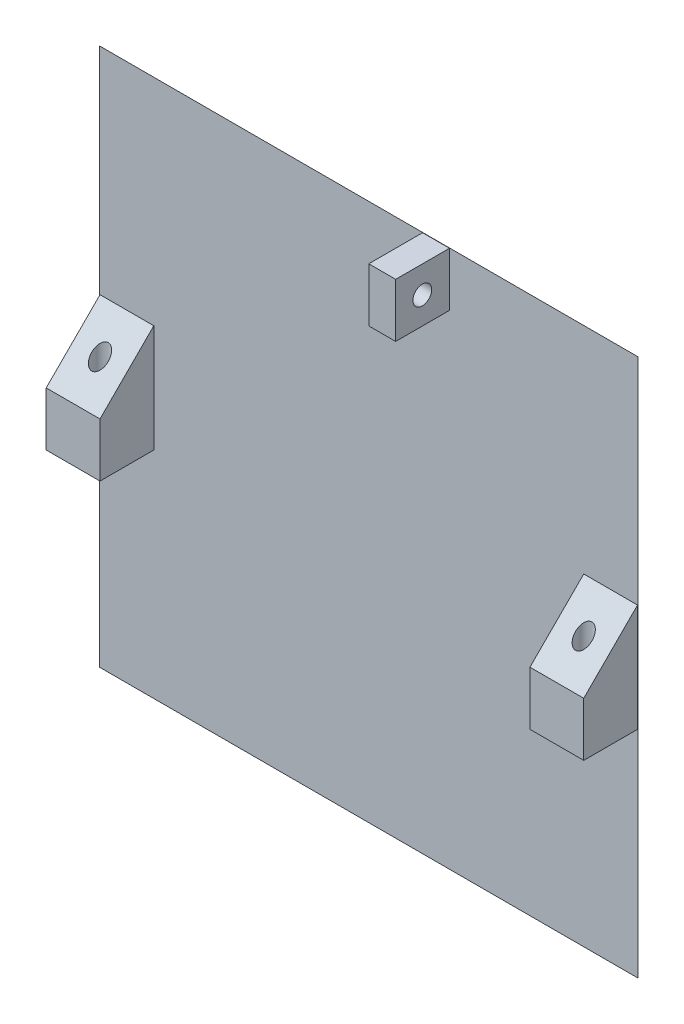
SolidWorks part; units mm, degrees
ref_plane "Plan de face" through (0, 0, 0) normal (0, 0, 1) x (1, 0, 0)
ref_plane "Plan de dessus" through (0, 0, 0) normal (0, 1, 0) x (1, 0, 0)
ref_plane "Plan de droite" through (0, 0, 0) normal (1, 0, 0) x (0, 0, -1)
sketch "Esquisse1" plane through (0, 0, 0) normal (0, 0, 1) x (1, 0, 0)
  line L1 (0, 100) -> (100, 100)
  line L2 (0, 100) -> (0, 0)
  line L3 (0, 0) -> (100, 0)
  line L4 (100, 100) -> (100, 0)
  dimension "D1" = 100
  dimension "D2" = 100
extrude "Boss.-Extru.1" add sketch "Esquisse1" along normal blind 3
sketch "Esquisse2" plane through (0, 0, 3) normal (0, 0, 1) x (1, 0, 0)
  line L0 (0, 100) -> (0, 0) construction
  line L1 (0.05, 60) -> (10.05, 60)
  line L2 (0.05, 60) -> (0.05, 40)
  line L3 (0.05, 40) -> (10.05, 40)
  line L4 (10.05, 60) -> (10.05, 40)
  line L5 (100, 100) -> (0, 100) construction
  line L6 (89.95, 60) -> (99.95, 60)
  line L7 (89.95, 60) -> (89.95, 40)
  line L8 (89.95, 40) -> (99.95, 40)
  line L9 (99.95, 60) -> (99.95, 40)
  line L10 (100, 0) -> (100, 100) construction
  dimension "D1" = 0.05
  dimension "D2" = 10
  dimension "D3" = 40
  dimension "D4" = 20
  dimension "D5" = 20
  dimension "D6" = 10
  dimension "D7" = 0.05
  dimension "D8" = 40
extrude "Boss.-Extru.2" add sketch "Esquisse2" along normal blind 10
chamfer "Chanfrein1" distance 10 angle 45 2 edges at (94.95, 60, 13) (5.05, 60, 13)
sketch "Esquisse3" plane through (0, 40, 0) normal (0, -1, 0) x (1, 0, 0)
  line L0 (10.05, 13) -> (10.05, 3) construction
  line L1 (0.05, 13) -> (10.05, 13) construction
  line L2 (99.95, 13) -> (99.95, 3) construction
  line L3 (89.95, 13) -> (99.95, 13) construction
  circle A0 centre (5.0462, 8) radius 1.525
  circle A1 centre (94.95, 8) radius 1.525
  dimension "D1" = 3.05
  dimension "D2" = 5.0038
  dimension "D3" = 5
  dimension "D4" = 3.05
  dimension "D5" = 5
  dimension "D6" = 5
extrude "Enlèv. mat.-Extru.1" cut sketch "Esquisse3" against normal through all
chamfer "Chanfrein2" distance 3 angle 45 4 edges at (50, 0, 0) (100, 50, 0) (50, 100, 0) (0, 50, 0)
sketch "Esquisse4" plane through (0, 0, 3) normal (0, 0, 1) x (1, 0, 0)
  line L0 (100, 100) -> (0, 100) construction
  line L1 (65, 99.95) -> (60, 99.95)
  line L2 (65, 99.95) -> (65, 89.95)
  line L3 (65, 89.95) -> (60, 89.95)
  line L4 (60, 99.95) -> (60, 89.95)
  line L5 (100, 0) -> (100, 100) construction
  dimension "D1" = 5
  dimension "D2" = 10
  dimension "D3" = 0.05
  dimension "D4" = 40
extrude "Boss.-Extru.3" add sketch "Esquisse4" along normal blind 10
sketch "Esquisse5" plane through (65, 0, 0) normal (1, 0, 0) x (0, 0, -1)
  line L0 (-3, 89.95) -> (-3, 99.95) construction
  line L1 (-13, 99.95) -> (-3, 99.95) construction
  circle A0 centre (-8.05, 94.95) radius 1.75
  dimension "D1" = 3.5
  dimension "D2" = 5.05
  dimension "D3" = 5
extrude "Enlèv. mat.-Extru.2" cut sketch "Esquisse5" against normal blind 10 contours A0
